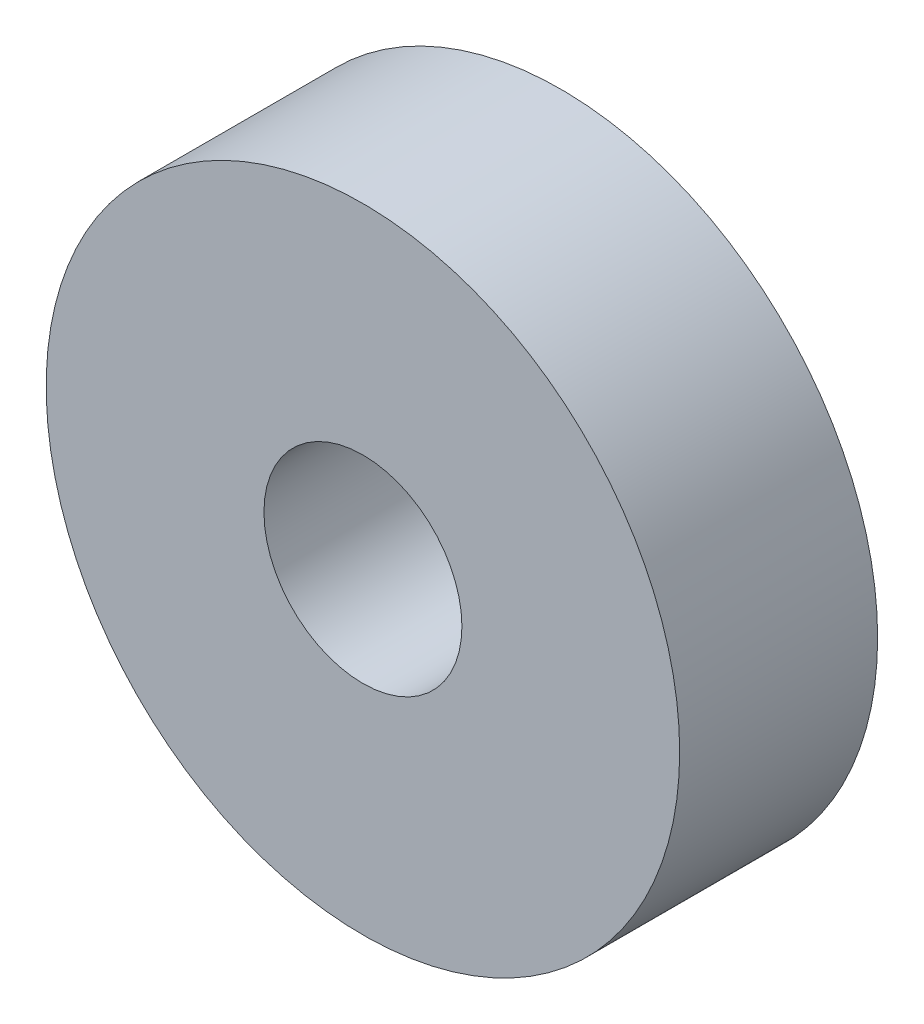
SolidWorks part; units mm, degrees
ref_plane "Front" through (0, 0, 0) normal (0, 0, 1) x (1, 0, 0)
ref_plane "Top" through (0, 0, 0) normal (0, 1, 0) x (1, 0, 0)
ref_plane "Right" through (0, 0, 0) normal (1, 0, 0) x (0, 0, -1)
sketch "Skizze1" plane through (0, 0, 0) normal (0, 0, 1) x (1, 0, 0)
  circle A0 centre (0, 0) radius 8
  circle A1 centre (0, 0) radius 2.5
  dimension "D1" = 16
  dimension "D2" = 5
extrude "Aufsatz-Linear austragen1" add sketch "Skizze1" along normal mid plane 5
